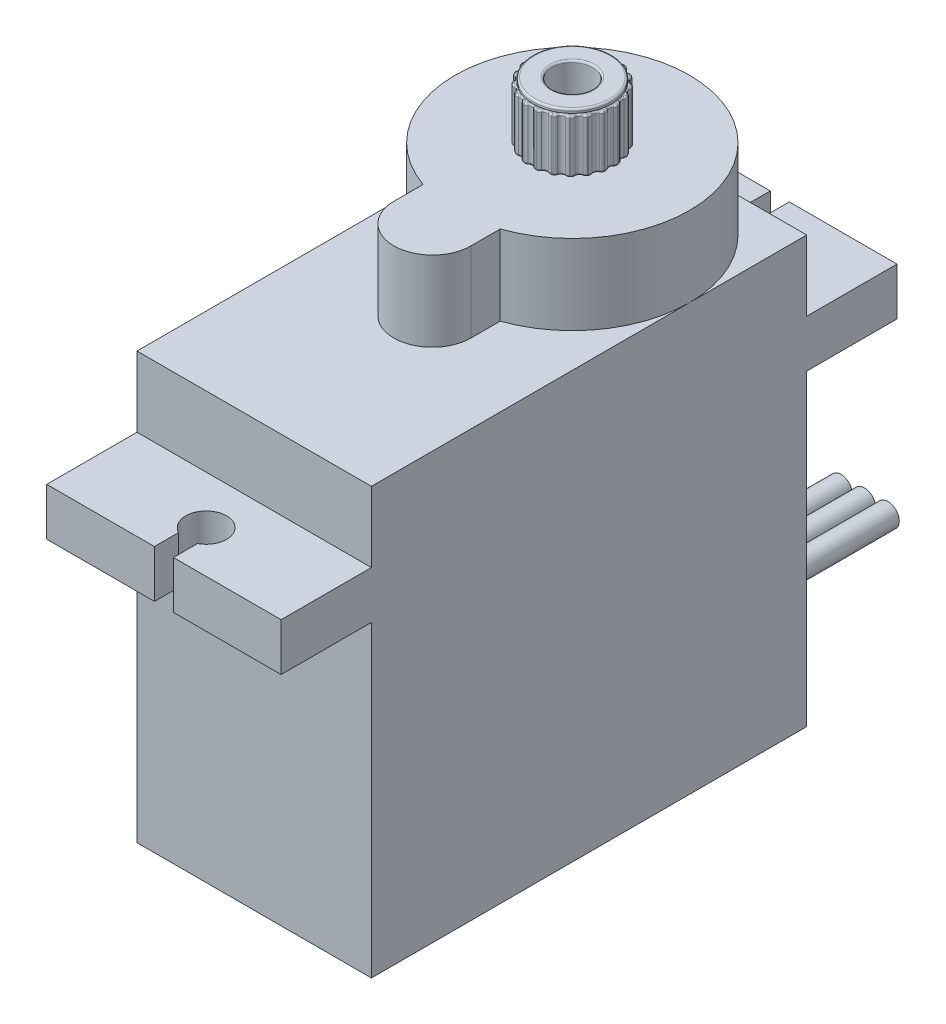
SolidWorks part; units mm, degrees
ref_plane "Front" through (0, 0, 0) normal (0, 0, 1) x (1, 0, 0)
ref_plane "Top" through (0, 0, 0) normal (0, 1, 0) x (1, 0, 0)
ref_plane "Right" through (0, 0, 0) normal (1, 0, 0) x (0, 0, -1)
sketch "Sketch1" plane through (0, 0, 0) normal (0, 1, 0) x (1, 0, 0)
  line L1 (-6.165, -11.45) -> (6.165, -11.45)
  line L2 (-6.165, -11.45) -> (-6.165, 11.45)
  line L3 (-6.165, 11.45) -> (6.165, 11.45)
  line L4 (6.165, -11.45) -> (6.165, 11.45)
  line L5 (-6.165, -11.45) -> (6.165, 11.45) construction
  line L6 (-6.165, 11.45) -> (6.165, -11.45) construction
  point P0 (0, 0)
  dimension "D1" = 12.33
  dimension "D2" = 22.9
extrude "Boss-Extrude1" add sketch "Sketch1" along normal blind 22.4
sketch "Sketch2" plane through (0, 22.4, 0) normal (0, 1, 0) x (1, 0, 0)
  line L0 (6.165, -11.45) -> (6.165, 11.45) construction
  line L1 (-6.165, -16.2) -> (6.165, -16.2)
  line L2 (-6.165, -16.2) -> (-6.165, 16.2)
  line L3 (-6.165, 16.2) -> (6.165, 16.2)
  line L4 (6.165, -16.2) -> (6.165, 16.2)
  line L5 (-6.165, -16.2) -> (6.165, 16.2) construction
  line L6 (-6.165, 16.2) -> (6.165, -16.2) construction
  point P0 (0, 0)
  dimension "D1" = 32.4
extrude "Boss-Extrude2" add sketch "Sketch2" against normal blind 2.5 from offset 3.7 offset against normal yes
sketch "Sketch3" plane through (0, 0, 0) normal (0, 1, 0) x (1, 0, 0)
  line L0 (0, 16.2) -> (0, 13.9764) construction
  line L1 (6.165, 16.2) -> (-6.165, 16.2) construction
  line L3 (-0.5, 17.472) -> (0.5, 17.472)
  line L4 (-0.5, 17.472) -> (-0.5, 14.928)
  line L5 (-0.5, 14.928) -> (0.5, 14.928)
  line L6 (0.5, 17.472) -> (0.5, 14.928)
  line L7 (-0.5, 17.472) -> (0.5, 14.928) construction
  line L8 (-0.5, 14.928) -> (0.5, 17.472) construction
  circle A0 centre (0, 13.9764) radius 1.075
  dimension "D2" = 2.15
  dimension "D1" = 1
extrude "Cut-Extrude1" cut sketch "Sketch3" along normal through all contours L5 A0 | A0 L6 L3 L4 | L5 A0 region at (0, 0, -16.2413) region at (0, 0, -14.9776) region at (0, 0, -13.9529)
mirror "Mirror1" about plane through (0, 0, 0) normal (0, 0, 1) of "Cut-Extrude1"
sketch "Sketch4" plane through (0, 22.4, 0) normal (0, 1, 0) x (1, 0, 0)
  line L0 (0, 0) -> (0, 11.45) construction
  line L1 (6.165, 11.45) -> (-6.165, 11.45) construction
  line L2 (6.165, -11.45) -> (6.165, 11.45) construction
  line L3 (0, 5.285) -> (0, -2.0761) construction
  line L4 (2.028, 5.285) -> (2.028, -2.0761)
  line L5 (-2.028, 5.285) -> (-2.028, -2.0761)
  line L6 (-6.165, 11.45) -> (6.165, 11.45) construction
  circle A0 centre (0, 5.285) radius 6.165
  arc A1 (2.028, 5.285) -> (-2.028, 5.285) centre (0, 5.285) ccw
  arc A2 (-2.028, -2.0761) -> (2.028, -2.0761) centre (0, -2.0761) ccw
  point P10 (0, 1.6044)
extrude "Boss-Extrude3" add sketch "Sketch4" along normal blind 4.2 contours A1 L4 A0 L5 | L4 A1 L5 A0 | L5 A2 L4 A0 region at (0, 22.4, -7.485) region at (0, 22.4, -3.0681) region at (0, 22.4, 2.2514)
sketch "Sketch5" plane through (0, 0, -11.45) normal (0, 0, -1) x (-1, 0, 0)
  line L0 (0, 0) -> (0, 2.5981) construction
  line L1 (0, 2.5981) -> (1.235, 2.5981) construction
  line L2 (-1.835, 2.5981) -> (1.835, 2.5981) construction
  circle A0 centre (0, 2.5981) radius 0.6
  circle A1 centre (1.235, 2.5981) radius 0.6
  circle A2 centre (-1.235, 2.5981) radius 0.6
  dimension "D1" = 1.2
  dimension "D2" = 3.67
extrude "Boss-Extrude4" add sketch "Sketch5" along normal blind 9.2 separate body
sketch "Sketch6" plane through (0, 26.6, 0) normal (0, 1, 0) x (1, 0, 0)
  circle A0 centre (0, 5.285) radius 2.25
  dimension "D1" = 4.5
extrude "Boss-Extrude5" add sketch "Sketch6" along normal blind 3 separate body
sketch "Sketch7" plane through (0, 26.6, 0) normal (0, 1, 0) x (1, 0, 0)
  circle A0 centre (0, 2.9246) radius 0.2346
extrude "Cut-Extrude2" cut sketch "Sketch7" along normal blind 3
pattern_circular "CirPattern1" count 21 over 360 about axis through (0, 29.6, -5.285) along (0, -1, 0) of "Cut-Extrude2"
sketch "Sketch8" plane through (0, 29.6, 0) normal (0, 1, 0) x (1, 0, 0)
  circle A0 centre (0, 5.285) radius 2.0639
extrude "Cut-Extrude-Thin1" cut sketch "Sketch8" against normal blind 0.2 thin thin type one direction wall 1
sketch "Sketch9" plane through (0, 29.6, 0) normal (0, 1, 0) x (1, 0, 0)
  circle A0 centre (0, 5.285) radius 1.0659
extrude "Cut-Extrude3" cut sketch "Sketch9" against normal blind 2.2
fillet "Fillet1" radius 0.2 42 edges at (-0.5336, 28, -7.4708) (-0.1343, 28, -7.531) (0.1343, 28, -7.531) (0.5336, 28, -7.4708) (0.7904, 28, -7.3916) (1.1542, 28, -7.2164) (1.3762, 28, -7.065) (1.6722, 28, -6.7904) (1.8397, 28, -6.5803) (2.0416, 28, -6.2306) (2.1398, 28, -5.9805) (2.2297, 28, -5.5868) (2.2497, 28, -5.3189) (2.2196, 28, -4.9162) (2.1598, 28, -4.6542) (2.0123, 28, -4.2784) (1.8779, 28, -4.0457) (1.6261, 28, -3.73) (1.4292, 28, -3.5472) (0.8535, 28, -3.2031) (0.4676, 28, -3.0841) (0.2019, 28, -3.0441) (-0.2019, 28, -3.0441) (-0.4676, 28, -3.0841) (-0.8535, 28, -3.2031) (-1.0955, 28, -3.3197) (-1.4292, 28, -3.5472) (-1.6261, 28, -3.73) (-1.8779, 28, -4.0457) (-2.0123, 28, -4.2784) (-2.1598, 28, -4.6542) (-2.2196, 28, -4.9162) (-2.2497, 28, -5.3189) (-2.2297, 28, -5.5868) (-2.1398, 28, -5.9805) (-2.0416, 28, -6.2306) (-1.8397, 28, -6.5803) (-1.6722, 28, -6.7904) (-1.3762, 28, -7.065) (-1.1542, 28, -7.2164) (-0.7904, 28, -7.3916) (1.0955, 28, -3.3197)
fillet "Fillet2" radius 0.1 84 edges at (0.2266, 29.4, -3.0627) (0.3353, 29.4, -3.0601) (0.4385, 29.4, -3.0946) (0.6266, 29.4, -3.2537) (0.8715, 29.4, -3.2282) (0.9762, 29.4, -3.2578) (1.0647, 29.4, -3.3212) (1.1975, 29.4, -3.5286) (1.4391, 29.4, -3.5765) (1.5304, 29.4, -3.6356) (1.5962, 29.4, -3.7223) (1.662, 29.4, -3.9596) (1.8787, 29.4, -4.0765) (1.9486, 29.4, -4.16) (1.9859, 29.4, -4.2622) (1.9788, 29.4, -4.5084) (2.1515, 29.4, -4.684) (2.1936, 29.4, -4.7843) (2.1992, 29.4, -4.893) (2.1198, 29.4, -5.1261) (2.233, 29.4, -5.3449) (2.2437, 29.4, -5.4531) (2.217, 29.4, -5.5586) (2.0725, 29.4, -5.758) (2.1162, 29.4, -6.0004) (2.0945, 29.4, -6.107) (2.0379, 29.4, -6.1999) (1.841, 29.4, -6.3479) (1.8113, 29.4, -6.5924) (1.7591, 29.4, -6.6879) (1.6777, 29.4, -6.76) (1.4459, 29.4, -6.8433) (1.3455, 29.4, -7.0682) (1.2675, 29.4, -7.144) (1.1684, 29.4, -7.1889) (0.9223, 29.4, -7.2003) (0.7601, 29.4, -7.3855) (0.6632, 29.4, -7.435) (0.5553, 29.4, -7.4487) (0.3168, 29.4, -7.387) (0.1072, 29.4, -7.5163) (0, 29.4, -7.535) (-0.1072, 29.4, -7.5163) (-0.3168, 29.4, -7.387) (-0.5553, 29.4, -7.4487) (-0.6632, 29.4, -7.435) (-0.7601, 29.4, -7.3855) (-0.9223, 29.4, -7.2003) (-1.1684, 29.4, -7.1889) (-1.2675, 29.4, -7.144) (-1.3455, 29.4, -7.0682) (-1.4459, 29.4, -6.8433) (-1.6777, 29.4, -6.76) (-1.7591, 29.4, -6.6879) (-1.8113, 29.4, -6.5924) (-1.841, 29.4, -6.3479) (-2.0379, 29.4, -6.1999) (-2.0945, 29.4, -6.107) (-2.1162, 29.4, -6.0004) (-2.0725, 29.4, -5.758) (-2.217, 29.4, -5.5586) (-2.2437, 29.4, -5.4531) (-2.233, 29.4, -5.3449) (-2.1198, 29.4, -5.1261) (-2.1992, 29.4, -4.893) (-2.1936, 29.4, -4.7843) (-2.1515, 29.4, -4.684) (-1.9788, 29.4, -4.5084) (-1.9859, 29.4, -4.2622) (-1.9486, 29.4, -4.16) (-1.8787, 29.4, -4.0765) (-1.662, 29.4, -3.9596) (-1.5962, 29.4, -3.7223) (-1.5304, 29.4, -3.6356) (-1.4391, 29.4, -3.5765) (-1.1975, 29.4, -3.5286) (-1.0647, 29.4, -3.3212) (-0.9762, 29.4, -3.2578) (-0.8715, 29.4, -3.2282) (-0.6266, 29.4, -3.2537) (-0.4385, 29.4, -3.0946) (-0.3353, 29.4, -3.0601) (-0.2266, 29.4, -3.0627) (0, 29.4, -3.1592)
fillet "Fillet3" radius 0.1 84 edges at (1.4391, 26.6, -3.5765) (1.5304, 26.6, -3.6356) (1.5962, 26.6, -3.7223) (1.662, 26.6, -3.9596) (1.8787, 26.6, -4.0765) (1.9486, 26.6, -4.16) (1.9859, 26.6, -4.2622) (1.9788, 26.6, -4.5084) (2.1515, 26.6, -4.684) (2.1936, 26.6, -4.7843) (2.1992, 26.6, -4.893) (2.1198, 26.6, -5.1261) (2.233, 26.6, -5.3449) (2.2437, 26.6, -5.4531) (2.217, 26.6, -5.5586) (2.0725, 26.6, -5.758) (2.1162, 26.6, -6.0004) (2.0945, 26.6, -6.107) (2.0379, 26.6, -6.1999) (1.841, 26.6, -6.3479) (1.8113, 26.6, -6.5924) (1.7591, 26.6, -6.6879) (1.6777, 26.6, -6.76) (1.4459, 26.6, -6.8433) (1.3455, 26.6, -7.0682) (1.2675, 26.6, -7.144) (1.1684, 26.6, -7.1889) (0.9223, 26.6, -7.2003) (0.7601, 26.6, -7.3855) (0.6632, 26.6, -7.435) (0.5553, 26.6, -7.4487) (0.3168, 26.6, -7.387) (0.1072, 26.6, -7.5163) (0, 26.6, -7.535) (-0.1072, 26.6, -7.5163) (-0.3168, 26.6, -7.387) (-0.5553, 26.6, -7.4487) (-0.6632, 26.6, -7.435) (-0.7601, 26.6, -7.3855) (-0.9223, 26.6, -7.2003) (-1.1684, 26.6, -7.1889) (-1.2675, 26.6, -7.144) (-1.3455, 26.6, -7.0682) (-1.4459, 26.6, -6.8433) (-1.6777, 26.6, -6.76) (-1.7591, 26.6, -6.6879) (-1.8113, 26.6, -6.5924) (-1.841, 26.6, -6.3479) (-2.0379, 26.6, -6.1999) (-2.0945, 26.6, -6.107) (-2.1162, 26.6, -6.0004) (-2.0725, 26.6, -5.758) (-2.217, 26.6, -5.5586) (-2.2437, 26.6, -5.4531) (-2.233, 26.6, -5.3449) (-2.1198, 26.6, -5.1261) (-2.1992, 26.6, -4.893) (-2.1936, 26.6, -4.7843) (-2.1515, 26.6, -4.684) (-1.9788, 26.6, -4.5084) (-1.9859, 26.6, -4.2622) (-1.9486, 26.6, -4.16) (-1.8787, 26.6, -4.0765) (-1.662, 26.6, -3.9596) (-1.5962, 26.6, -3.7223) (-1.5304, 26.6, -3.6356) (-1.4391, 26.6, -3.5765) (-1.1975, 26.6, -3.5286) (-1.0647, 26.6, -3.3212) (-0.9762, 26.6, -3.2578) (-0.8715, 26.6, -3.2282) (-0.6266, 26.6, -3.2537) (-0.4385, 26.6, -3.0946) (-0.3353, 26.6, -3.0601) (-0.2266, 26.6, -3.0627) (0, 26.6, -3.1592) (0.2266, 26.6, -3.0627) (0.3353, 26.6, -3.0601) (0.4385, 26.6, -3.0946) (0.6266, 26.6, -3.2537) (0.8715, 26.6, -3.2282) (0.9762, 26.6, -3.2578) (1.0647, 26.6, -3.3212) (1.1975, 26.6, -3.5286)
fillet "Fillet4" radius 0.1 2 edges at (0, 29.6, -3.2211) (0, 29.6, -4.2191)
sketch "Sketch10" plane through (0, 0, 0) normal (0, 1, 0) x (1, 0, 0)
  line L0 (6.165, 16.2) -> (0.5, 16.2) construction
  line L1 (0.5, 16.2) -> (0.5, 14.928) construction
  line L2 (-0.5, 14.928) -> (-0.5, 16.2) construction
  line L3 (-0.5, 16.2) -> (-6.165, 16.2) construction
  line L4 (-6.165, 16.2) -> (-6.165, 11.45) construction
  line L5 (-6.165, 11.45) -> (6.165, 11.45) construction
  line L6 (6.165, 11.45) -> (6.165, 16.2) construction
  line L7 (-6.165, -16.2) -> (-0.5, -16.2) construction
  line L8 (-0.5, -16.2) -> (-0.5, -14.928) construction
  line L9 (0.5, -14.928) -> (0.5, -16.2) construction
  line L10 (0.5, -16.2) -> (6.165, -16.2) construction
  line L11 (6.165, -16.2) -> (6.165, -11.45) construction
  line L12 (6.165, -11.45) -> (-6.165, -11.45) construction
  line L13 (-6.165, -11.45) -> (-6.165, -16.2) construction
  line L14 (6.165, 16.2) -> (0.5, 16.2)
  line L15 (0.5, 16.2) -> (0.5, 14.928)
  line L16 (-0.5, 14.928) -> (-0.5, 16.2)
  line L17 (-0.5, 16.2) -> (-6.165, 16.2)
  line L18 (-6.165, 16.2) -> (-6.165, 11.45)
  line L19 (-6.165, 11.45) -> (6.165, 11.45)
  line L20 (6.165, 11.45) -> (6.165, 16.2)
  line L21 (-6.165, -16.2) -> (-0.5, -16.2)
  line L22 (-0.5, -16.2) -> (-0.5, -14.928)
  line L23 (0.5, -14.928) -> (0.5, -16.2)
  line L24 (0.5, -16.2) -> (6.165, -16.2)
  line L25 (6.165, -16.2) -> (6.165, -11.45)
  line L26 (6.165, -11.45) -> (-6.165, -11.45)
  line L27 (-6.165, -11.45) -> (-6.165, -16.2)
  arc A0 (-0.5, 14.928) -> (0.5, 14.928) centre (0, 13.9764) ccw construction
  arc A1 (0.5, -14.928) -> (-0.5, -14.928) centre (0, -13.9764) ccw construction
  arc A2 (-0.5, 14.928) -> (0.5, 14.928) centre (0, 13.9764) ccw
  arc A3 (0.5, -14.928) -> (-0.5, -14.928) centre (0, -13.9764) ccw
  circle A5 centre (0, 5.285) radius 1.9639
  circle A6 centre (0, 5.285) radius 1.9639
  dimension "D1" = 0
delete or keep bodies "Body-Delete/Keep 1" [suppressed] type delete bodies bodies 107 108 106
sketch "Sketch11" plane through (0, 26.6, 0) normal (0, 1, 0) x (1, 0, 0)
  circle A0 centre (0, 5.285) radius 2.7
  dimension "D1" = 5.4
delete or keep bodies "Body-Delete/Keep 2" [suppressed] type delete bodies bodies 107 108 106
sketch "Sketch12" plane through (0, 0, 0) normal (0, 1, 0) x (1, 0, 0)
  line L0 (0, 13.9764) -> (0, -13.9764) construction
  circle A0 centre (0, 5.285) radius 2.6425
  circle A1 centre (0, 0) radius 2.6425
sketch "Sketch13" plane through (0, 0, 0) normal (0, 1, 0) x (1, 0, 0)
  circle A0 centre (0, 5.285) radius 20
  dimension "D1" = 40
